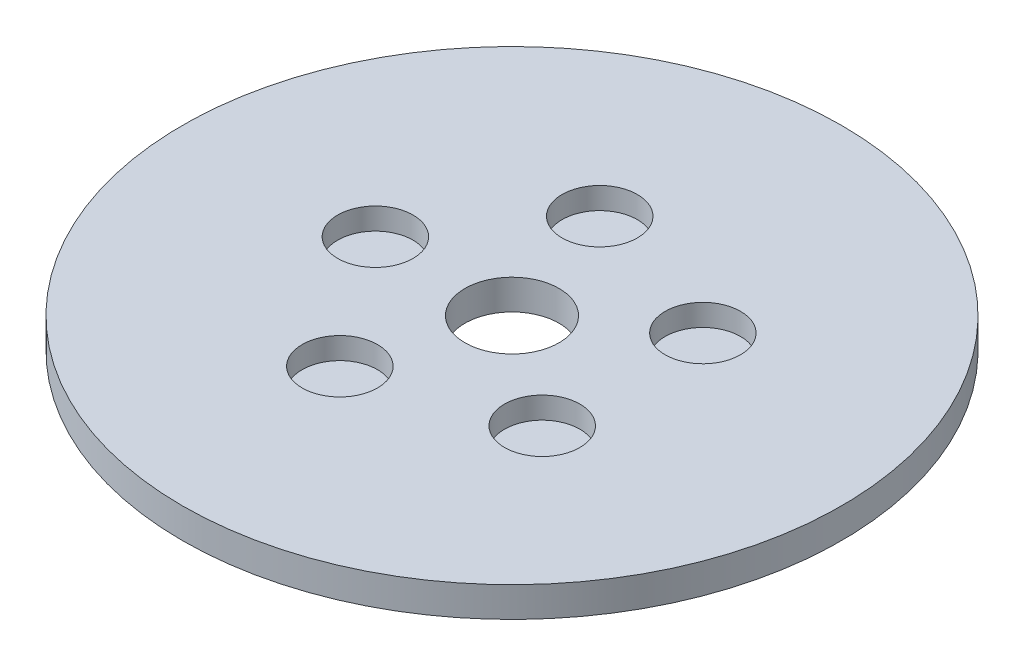
SolidWorks part; units mm, degrees
ref_plane "Front Plane" through (0, 0, 0) normal (0, 0, 1) x (1, 0, 0)
ref_plane "Top Plane" through (0, 0, 0) normal (0, 1, 0) x (1, 0, 0)
ref_plane "Right Plane" through (0, 0, 0) normal (1, 0, 0) x (0, 0, -1)
sketch "Sketch1" plane through (0, 0, 0) normal (0, 1, 0) x (1, 0, 0)
  circle A0 centre (0, 0) radius 87.5
  dimension "FLANGE_OD" = 175
extrude "Boss-Extrude1" add sketch "Sketch1" along normal blind 8
sketch "Sketch2" plane through (0, 0, 0) normal (0, 1, 0) x (1, 0, 0)
  circle A0 centre (0, 0) radius 12.5
  dimension "BORE_D" = 25
extrude "Cut-Extrude1" cut sketch "Sketch2" along normal through all
sketch "Sketch3" plane through (0, 8, 0) normal (0, 1, 0) x (1, 0, 0)
  circle A0 centre (0, 0) radius 36.2746 construction
  circle A1 centre (-36.2746, 0) radius 10
  dimension "BOLT_D" = 20
  dimension "BOLT_PCD" = 72.5493
extrude "Cut-Extrude2" cut sketch "Sketch3" against normal blind 5.7809
pattern_circular "CirPattern1" count 5 over 360 about axis through (0, 0, 0) along (0, 1, 0) of "Cut-Extrude2"
